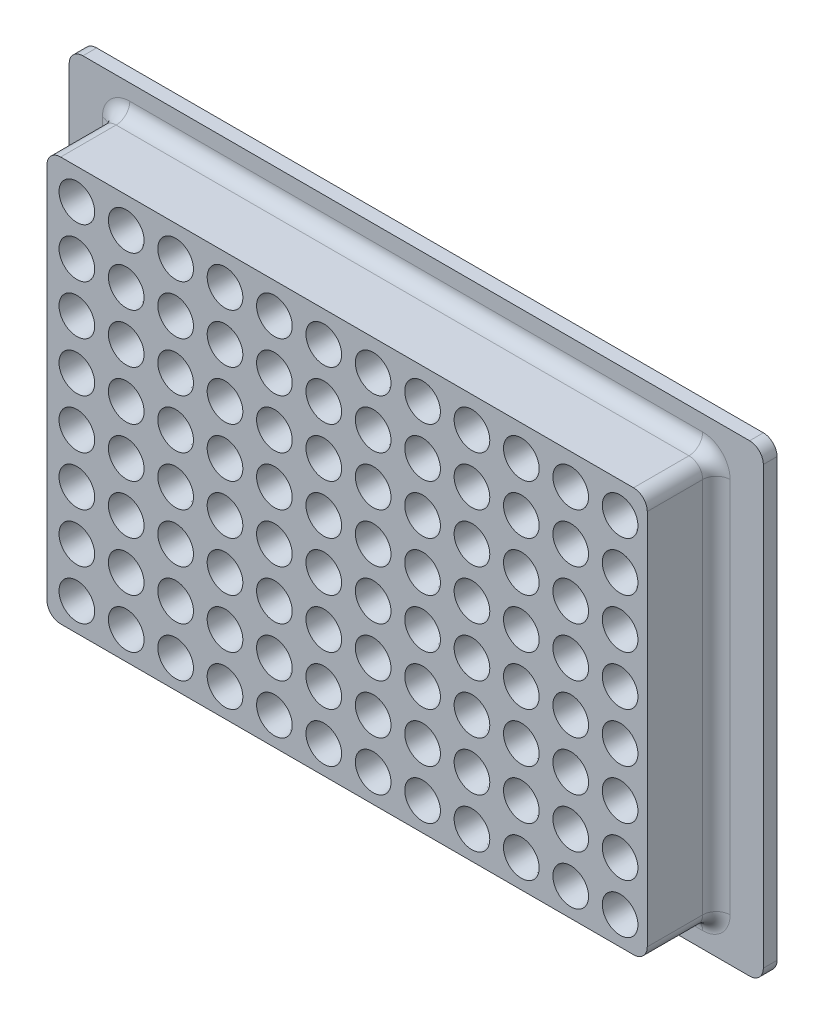
SolidWorks part; units mm, degrees
ref_plane "Front Plane" through (0, 0, 0) normal (0, 0, 1) x (1, 0, 0)
ref_plane "Top Plane" through (0, 0, 0) normal (0, 1, 0) x (1, 0, 0)
ref_plane "Right Plane" through (0, 0, 0) normal (1, 0, 0) x (0, 0, -1)
sketch "Sketch1" plane through (0, 0, 0) normal (0, 0, 1) x (1, 0, 0)
  line L1 (0, 0) -> (126.5, 0)
  line L2 (0, 0) -> (0, 84.5)
  line L3 (0, 84.5) -> (126.5, 84.5)
  line L4 (126.5, 0) -> (126.5, 84.5)
  dimension "D1" = 84.5
  dimension "D2" = 126.5
extrude "Boss-Extrude1" add sketch "Sketch1" along normal blind 2.5
sketch "Sketch3" plane through (0, 0, 2.5) normal (0, 0, 1) x (1, 0, 0)
  line L0 (0, 0) -> (126.5, 0) construction
  line L1 (8.55, 79.1) -> (117.95, 79.1)
  line L2 (8.55, 79.1) -> (8.55, 5.4)
  line L3 (8.55, 5.4) -> (117.95, 5.4)
  line L4 (117.95, 79.1) -> (117.95, 5.4)
  line L5 (0, 84.5) -> (0, 0) construction
  point P4 (63.25, 5.4)
  point P7 (63.25, 0)
  point P8 (8.55, 42.25)
  point P11 (0, 42.25)
  dimension "D1" = 73.7
  dimension "D2" = 109.4
extrude "Boss-Extrude2" add sketch "Sketch3" along normal blind 12.6
fillet "Fillet1" radius 2.5 12 edges at (126.5, 0, 1.25) (0, 0, 1.25) (126.5, 84.5, 1.25) (0, 84.5, 1.25) (63.25, 5.4, 2.5) (117.95, 42.25, 2.5) (8.55, 5.4, 8.8) (117.95, 5.4, 8.8) (117.95, 79.1, 8.8) (8.55, 79.1, 8.8) (63.25, 79.1, 2.5) (8.55, 42.25, 2.5)
sketch "Sketch2" plane through (0, 0, 15.1) normal (0, 0, 1) x (1, 0, 0)
  line L0 (0, 82) -> (0, 2.5) construction
  line L1 (124, 84.5) -> (2.5, 84.5) construction
  circle A0 centre (14, 73.5) radius 3.25
  dimension "D1" = 6.5
  dimension "D2" = 14
  dimension "D3" = 11
extrude "Cut-Extrude1" cut sketch "Sketch2" against normal blind 13 draft 10
pattern_linear "LPattern1" count 12 spacing 9 along (1, 0, 0) count 8 spacing 9 along (0, -1, 0) of "Cut-Extrude1"
